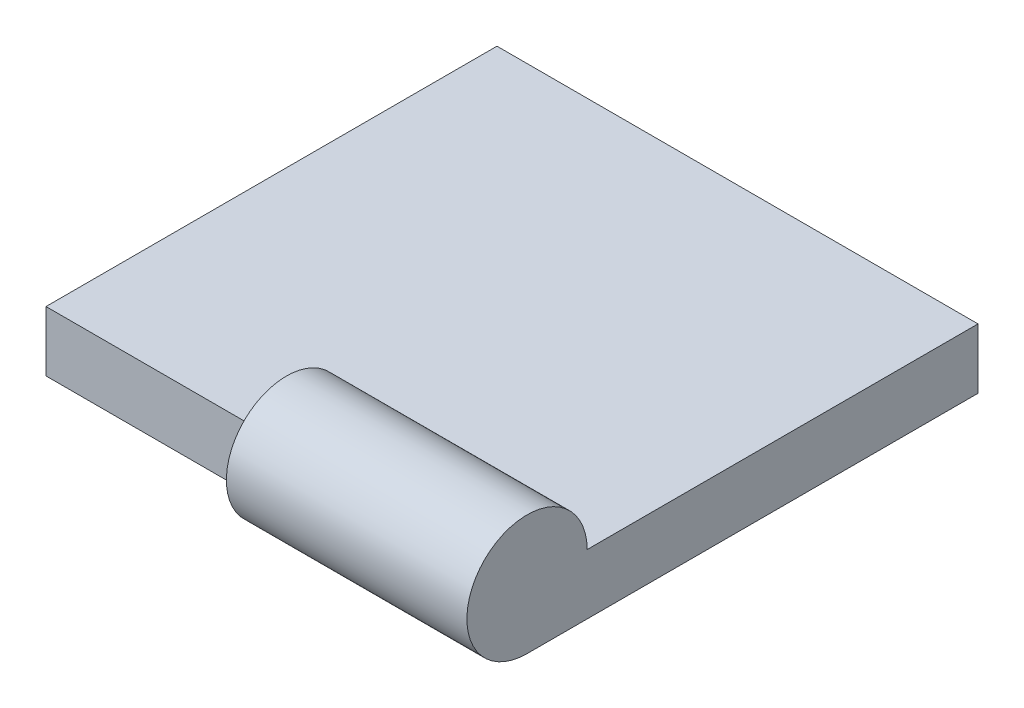
SolidWorks part; units mm, degrees
ref_plane "Front Plane" through (0, 0, 0) normal (0, 0, 1) x (1, 0, 0)
ref_plane "Top Plane" through (0, 0, 0) normal (0, 1, 0) x (1, 0, 0)
ref_plane "Right Plane" through (0, 0, 0) normal (1, 0, 0) x (0, 0, -1)
sketch "Sketch1" plane through (0, 0, 0) normal (0, 1, 0) x (1, 0, 0)
  line L2 (18.0696, -158.0434) -> (2.0696, -158.0434)
  line L3 (18.0696, -158.0434) -> (18.0696, -173.0434)
  line L4 (18.0696, -173.0434) -> (2.0696, -173.0434)
  line L5 (2.0696, -158.0434) -> (2.0696, -173.0434)
  dimension "D1" = 15
  dimension "D2" = 16
extrude "Boss-Extrude1" add sketch "Sketch1" along normal blind 2
sketch "Sketch2" plane through (18.0696, 0, 0) normal (1, 0, 0) x (0, 0, -1)
  circle A0 centre (-173.0434, 2) radius 2
extrude "Boss-Extrude2" add sketch "Sketch2" against normal blind 8
